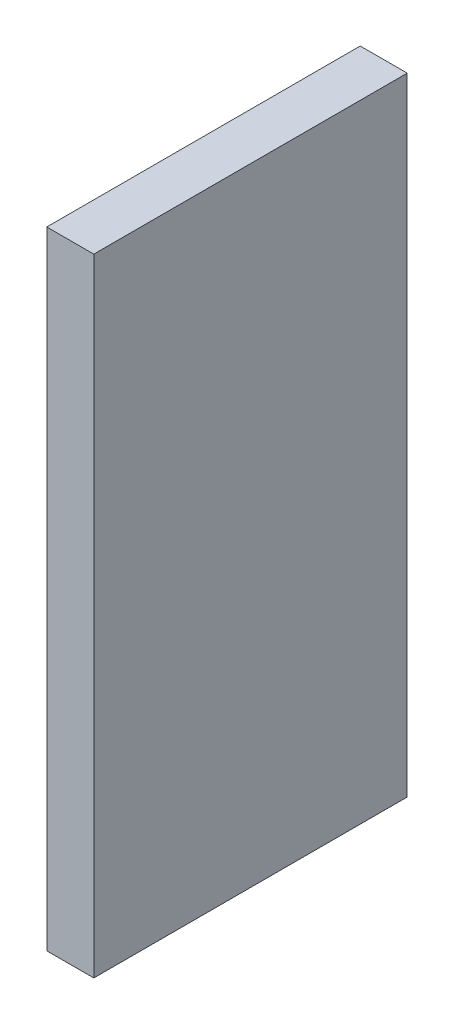
SolidWorks part; units mm, degrees
ref_plane "Front Plane" through (0, 0, 0) normal (1, 0, 0) x (0, 1, 0)
ref_plane "Top Plane" through (0, 0, 0) normal (0, 0, 1) x (0, 1, 0)
ref_plane "Right Plane" through (0, 0, 0) normal (0, 1, 0) x (-1, 0, 0)
sketch "Sketch1" plane through (0, 0, 0) normal (1, 0, 0) x (0, 1, 0)
  line L7 (-40, -20) -> (40, -20)
  line L8 (-40, -20) -> (-40, 20)
  line L9 (-40, 20) -> (40, 20)
  line L10 (40, -20) -> (40, 20)
  line L11 (-40, -20) -> (40, 20) construction
  line L12 (-40, 20) -> (40, -20) construction
  point P0 (0, 0)
  dimension "D1" = 80
  dimension "D2" = 40
extrude "Boss-Extrude2" add sketch "Sketch1" along normal blind 6 contours L7 L10 L9 L8
